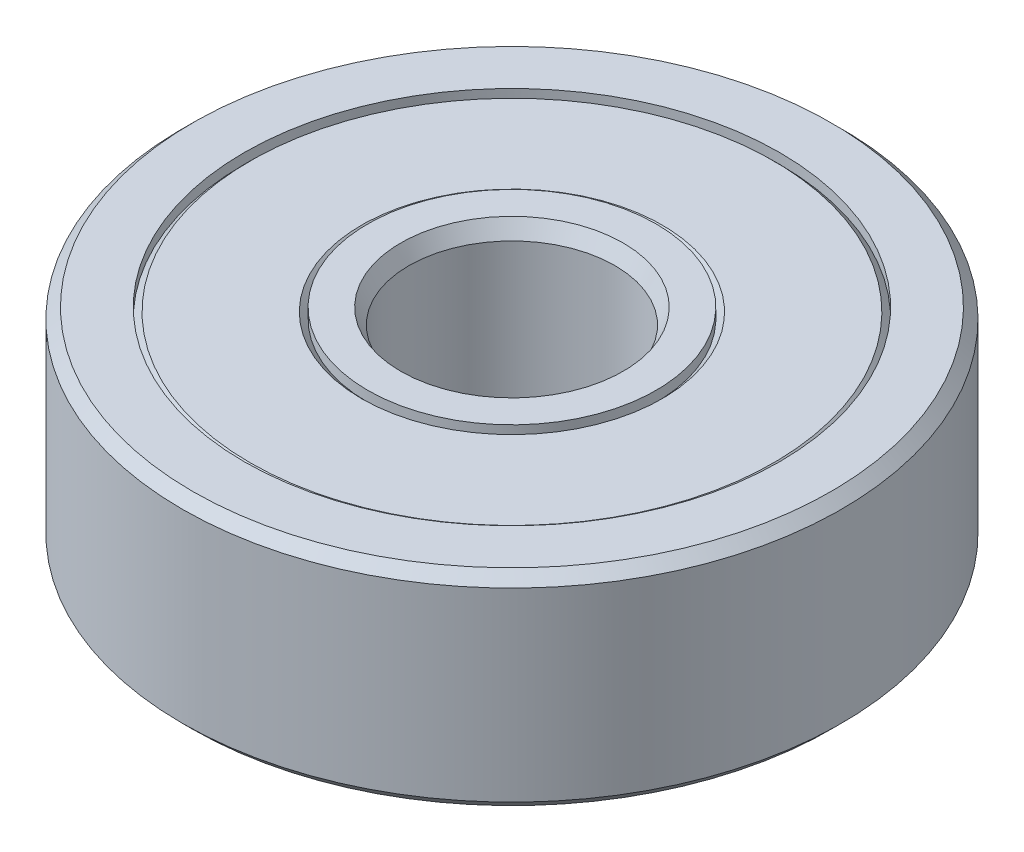
SolidWorks part; units mm, degrees
ref_plane "Спереди" through (0, 0, 0) normal (0, 0, 1) x (1, 0, 0)
ref_plane "Сверху" through (0, 0, 0) normal (0, 1, 0) x (1, 0, 0)
ref_plane "Справа" through (0, 0, 0) normal (1, 0, 0) x (0, 0, -1)
sketch "Эскиз1" plane through (0, 0, 0) normal (0, 1, 0) x (1, 0, 0)
  circle A0 centre (0, 0) radius 8
  circle A1 centre (0, 0) radius 6.5
  circle A2 centre (0, 0) radius 2.5
  circle A3 centre (0, 0) radius 3.5
extrude "Бобышка-Вытянуть1" add sketch "Эскиз1" along normal blind 5 contours A3 A2 | A0 A1 region at (-7.7737, 0, 0) region at (-3.401, 0, 0)
extrude "Бобышка-Вытянуть2" add sketch "Эскиз1<3>" along normal blind 4.8 from offset 0.1 separate body contours A1 A3 region at (-6.3162, 0, 0)
sketch "Эскиз1<3>" plane through (0, 0, 0) normal (0, 1, 0) x (1, 0, 0) same geometry as "Эскиз1"
chamfer "Фаска1" distance 0.25 angle 45 2 edges at (0, 0, 8) (0, 5, 8)
chamfer "Фаска2" distance 0.2 angle 62 1 edges at (0, 5, 2.5) first distance on face at (0, 5, 2.5)
chamfer "Фаска3" distance 0.15 angle 45 4 edges at (0, 0.1, 6.5) (0, 0.1, 3.5) (0, 4.9, 6.5) (0, 4.9, 3.5)
sketch "Эскиз2" [suppressed] plane through (0, 0, 0) normal (0, 0, 1) x (1, 0, 0)
  line L0 (0, -1.8609) -> (0, 7.3557) construction
  line L1 (-8.2427, 2.5029) -> (-8.6009, 2.5029) construction
  line L2 (-7.3224, 2.5029) -> (-8.2427, 1.5826)
  line L3 (-7.3224, 2.5029) -> (-8.2427, 3.4231)
  line L4 (-8.2427, 3.4231) -> (-8.2427, 2.5029)
  line L5 (-8.2427, 2.5029) -> (-8.2427, 1.5826)
  dimension "D1" = 90
chamfer "Фаска4" distance 0.2 angle 62 1 edges at (0, 0, 2.5) first distance on face at (0, 0, 2.5)
